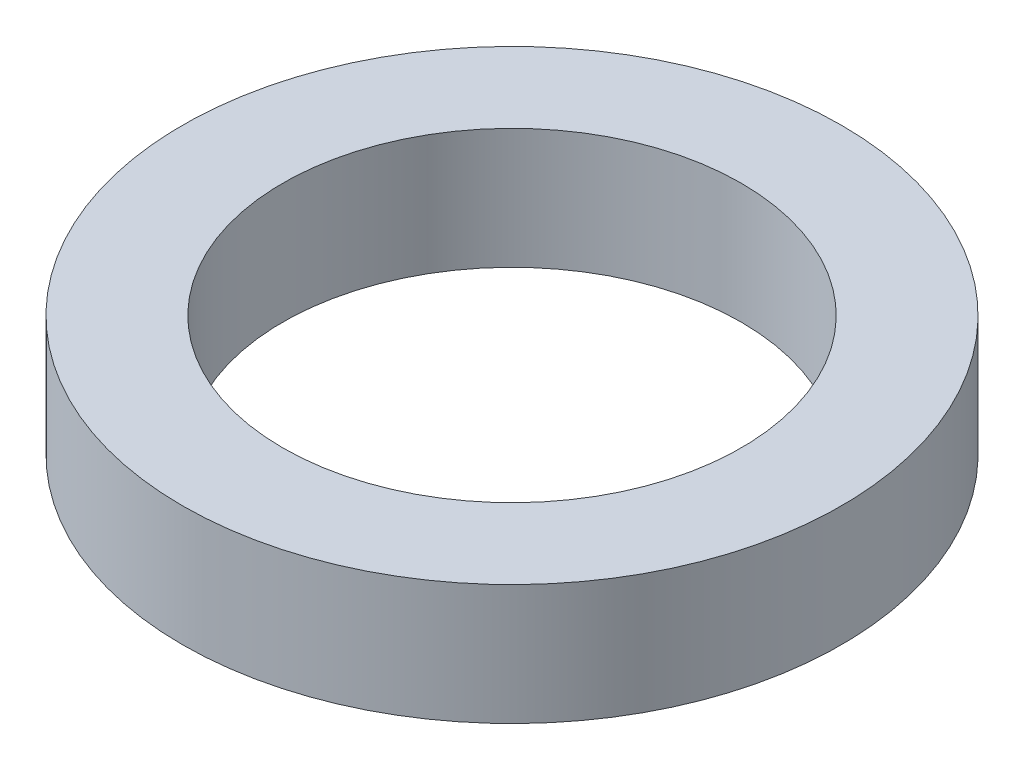
SolidWorks part; units mm, degrees
ref_plane "Front Plane" through (0, 0, 0) normal (0, 0, 1) x (1, 0, 0)
ref_plane "Top Plane" through (0, 0, 0) normal (0, 1, 0) x (1, 0, 0)
ref_plane "Right Plane" through (0, 0, 0) normal (1, 0, 0) x (0, 0, -1)
sketch "Sketch1" plane through (0, 0, 0) normal (0, 1, 0) x (1, 0, 0)
  circle A0 centre (0, 0) radius 57.5
  dimension "FLANGE_OD" = 115
extrude "Boss-Extrude1" add sketch "Sketch1" along normal blind 21
sketch "Sketch2" plane through (0, 0, 0) normal (0, 1, 0) x (1, 0, 0)
  circle A0 centre (0, 0) radius 40
  dimension "BORE_D" = 80
extrude "Cut-Extrude1" cut sketch "Sketch2" along normal through all
sketch "Sketch3" plane through (0, 21, 0) normal (0, 1, 0) x (1, 0, 0)
  circle A0 centre (0, 0) radius 26.1746 construction
  circle A1 centre (-26.1746, 0) radius 2.4711
  dimension "BOLT_D" = 4.9421
  dimension "BOLT_PCD" = 52.3492
extrude "Cut-Extrude2" cut sketch "Sketch3" against normal blind 20.6414 rebuild error yes
pattern_circular "CirPattern1" count 4 over 360 rebuild error yes
